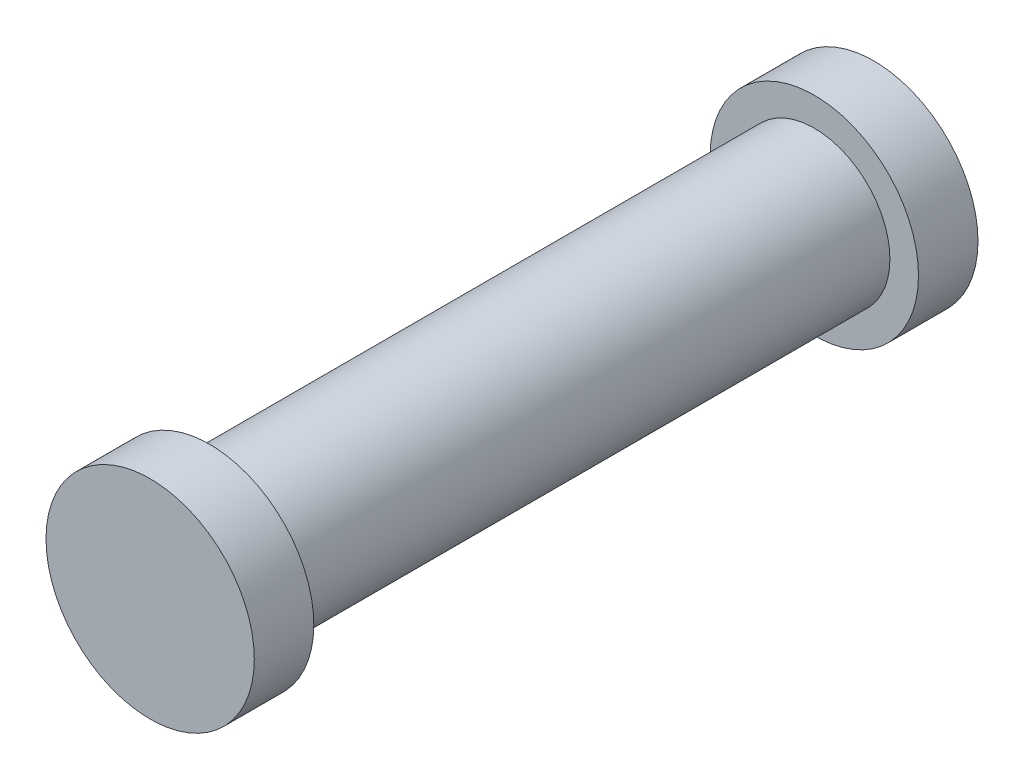
SolidWorks part; units mm, degrees
ref_plane "Front Plane" through (0, 0, 0) normal (0, 0, 1) x (1, 0, 0)
ref_plane "Top Plane" through (0, 0, 0) normal (0, 1, 0) x (1, 0, 0)
ref_plane "Right Plane" through (0, 0, 0) normal (1, 0, 0) x (0, 0, -1)
sketch "Sketch1" plane through (0, 0, 0) normal (0, 0, 1) x (1, 0, 0)
  circle A0 centre (0, 0) radius 12.7
  dimension "D1" = 25.4
extrude "Boss-Extrude1" add sketch "Sketch1" along normal mid plane 101.6
ref_axis "Axis1" through (0, 0, 141.9018) along (0, 0, -1)
sketch "Sketch2" plane through (0, 0, 50.8) normal (0, 0, 1) x (1, 0, 0)
  circle A0 centre (0, 0) radius 17.5
  dimension "D1" = 35
extrude "Boss-Extrude2" add sketch "Sketch2" along normal blind 10
mirror "Mirror1" about plane through (0, 0, 0) normal (0, 0, 1) of "Boss-Extrude2"
